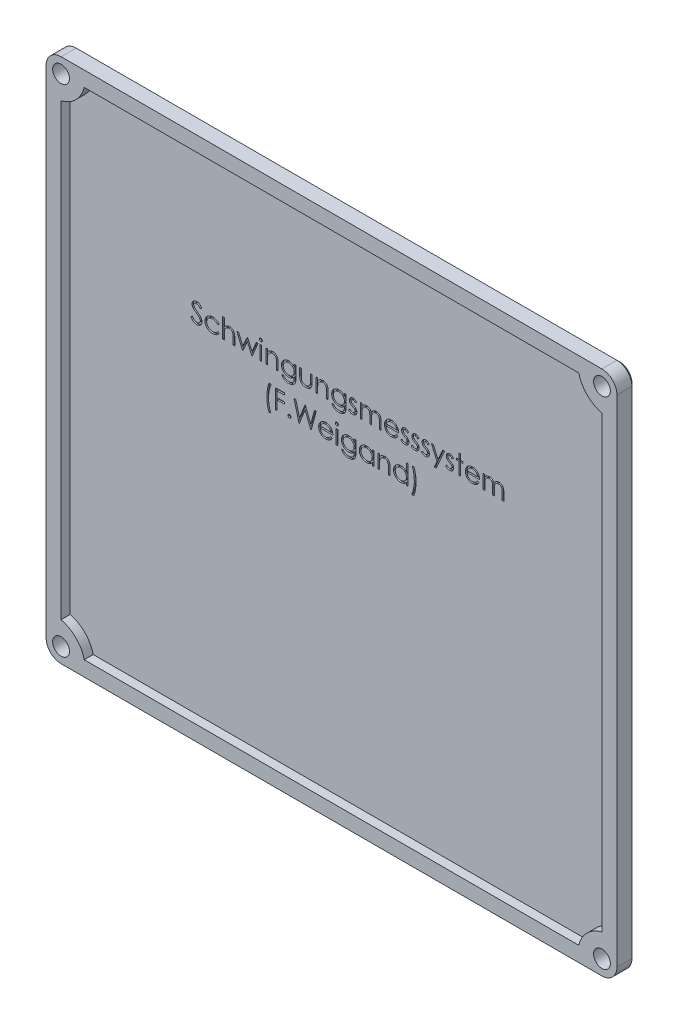
SolidWorks part; units mm, degrees
note: The reader was unsure of these and kept them because the rebuilt part matched: shared geometry of "Skizze1<2>", "Skizze2<5>".
ref_plane "Ebene vorne" through (0, 0, 0) normal (0, 0, 1) x (1, 0, 0)
ref_plane "Ebene oben" through (0, 0, 0) normal (0, 1, 0) x (1, 0, 0)
ref_plane "Ebene rechts" through (0, 0, 0) normal (1, 0, 0) x (0, 0, -1)
sketch "Skizze1" plane through (0, 0, 0) normal (0, 0, 1) x (1, 0, 0)
  line L1 (90, -82.5) -> (-90, -82.5)
  line L2 (90, -82.5) -> (90, 82.5)
  line L3 (90, 82.5) -> (-90, 82.5)
  line L4 (-90, -82.5) -> (-90, 82.5)
  line L5 (90, -82.5) -> (-90, 82.5) construction
  line L6 (90, 82.5) -> (-90, -82.5) construction
  line L7 (95, -87.5) -> (-95, -87.5)
  line L8 (95, -87.5) -> (95, 87.5)
  line L9 (95, 87.5) -> (-95, 87.5)
  line L10 (-95, -87.5) -> (-95, 87.5)
  line L11 (95, -87.5) -> (-95, 87.5) construction
  line L12 (95, 87.5) -> (-95, -87.5) construction
  point P0 (0, 0)
  point P5 (0, 0)
  dimension "D1" = 5
  dimension "D2" = 5
  dimension "D3" = 180
  dimension "D4" = 165
extrude "Aufsatz-Linear austragen1" add sketch "Skizze1" along normal blind 3
extrude "Aufsatz-Linear austragen2" add sketch "Skizze1<2>" against normal blind 3 contours L9 L10 L7 L8
sketch "Skizze1<2>" plane through (0, 0, 0) normal (0, 0, 1) x (1, 0, 0) same geometry as "Skizze1"
sketch "Skizze2" plane through (0, 0, 3) normal (0, 0, 1) x (1, 0, 0)
  line L0 (-92.5, 85) -> (-92.5, 74.5)
  line L1 (-92.5, 85) -> (-82, 85)
  line L2 (-92.5, 85) -> (-85.0754, 77.5754) construction
  line L3 (-95, 87.5) -> (-90, 82.5) construction
  line L4 (0, 9.9788) -> (0, -13.3423) construction
  line L5 (-10.3406, 0) -> (19.0775, 0) construction
  line L6 (92.5, 85) -> (92.5, 74.5)
  line L7 (92.5, 85) -> (82, 85)
  line L8 (92.5, -85) -> (82, -85)
  line L9 (92.5, -85) -> (92.5, -74.5)
  line L10 (-92.5, -85) -> (-92.5, -74.5)
  line L11 (-92.5, -85) -> (-82, -85)
  arc A0 (-92.5, 74.5) -> (-82, 85) centre (-92.5, 85) ccw
  circle A1 centre (-90.0251, 82.5251) radius 2.8
  arc A2 (92.5, 74.5) -> (82, 85) centre (92.5, 85) cw
  circle A3 centre (90.0251, 82.5251) radius 2.8
  arc A4 (92.5, -74.5) -> (82, -85) centre (92.5, -85) ccw
  circle A5 centre (90.0251, -82.5251) radius 2.8
  circle A6 centre (-90.0251, -82.5251) radius 2.8
  arc A7 (-92.5, -74.5) -> (-82, -85) centre (-92.5, -85) cw
  dimension "D1" = 7
  dimension "D2" = 10.5
  dimension "D3" = 5.6
extrude "Schnitt-Linear austragen2" cut sketch "Skizze2" against normal through all contours A1 | A3 | A5 | A6
fillet "Verrundung1" radius 5 4 edges at (-95, -87.5, 0) (95, -87.5, 0) (95, 87.5, 0) (-95, 87.5, 0)
chamfer "Fase1" distance 1 angle 45 8 edges at (93.5355, -86.0355, -3) (95, 0, -3) (93.5355, 86.0355, -3) (0, 87.5, -3) (-93.5355, 86.0355, -3) (-95, 0, -3) (-93.5355, -86.0355, -3) (0, -87.5, -3)
extrude "Aufsatz-Linear austragen3" add sketch "Skizze2<5>" against normal up to surface (3 mm away)
sketch "Skizze2<5>" plane through (0, 0, 3) normal (0, 0, 1) x (1, 0, 0) same geometry as "Skizze2"
sketch "Skizze3" plane through (0, 0, 0) normal (0, 0, 1) x (1, 0, 0)
  text T0 "Schwingungsmesssystem\r\n          (F.Weigand)" font "Century Gothic" height in points 24
  point P2 (0, 0)
  point P3 (0, 0)
  point P4 (0, 0)
  point P5 (0, 0)
  dimension "D1" = 50
  dimension "D2" = 30
extrude "Schnitt-Linear austragen3" cut sketch "Skizze3" against normal blind 0.5
equation "\"D2@Skizze1\"=\"D1@Skizze1\""
